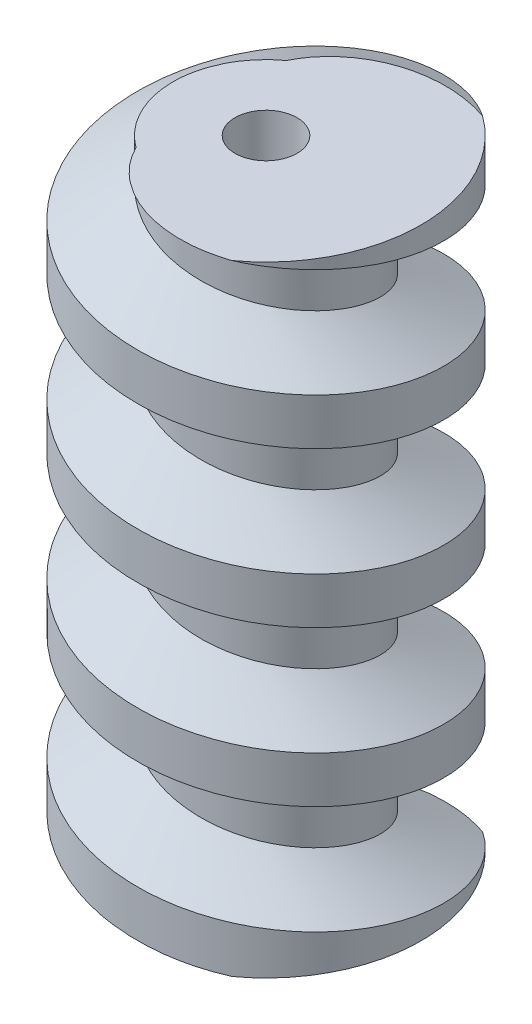
SolidWorks part; units mm, degrees
ref_plane "Front Plane" through (0, 0, 0) normal (0, 0, 1) x (1, 0, 0)
ref_plane "Top Plane" through (0, 0, 0) normal (0, 1, 0) x (1, 0, 0)
ref_plane "Right Plane" through (0, 0, 0) normal (1, 0, 0) x (0, 0, -1)
sketch "Sketch1" plane through (0, 0, 0) normal (0, 1, 0) x (1, 0, 0)
  circle A0 centre (0, 0) radius 10
  dimension "D1" = 20
extrude "Boss-Extrude1" add sketch "Sketch1" along normal blind 40 contours A0
sketch "Sketch2" plane through (0, 0, 0) normal (0, 1, 0) x (1, 0, 0)
  circle A1 centre (0, 0) radius 10
  circle A2 centre (0, 0) radius 10
  dimension "D1" = 0
curve "Helix/Spiral1" pitch 10 height 40 turns 4
ref_plane "Plane1" through (-10, 0, 0) normal (0, 0, 1) x (1, 0, 0)
sketch "Sketch3" plane through (-10, 0, 0) normal (0, 0, 1) x (1, 0, 0)
  line L1 (21.2864, 0) -> (-1.2864, 0) construction
  line L2 (0, 40) -> (0, 0) construction
  line L3 (0, 0) -> (4, 0) construction
  line L4 (4, -1.5) -> (4, 1.5)
  line L5 (4, 1.5) -> (0, 3.5)
  line L6 (4, -1.5) -> (0, -3.5)
  line L7 (0, -3.5) -> (-0.7038, -3.5)
  line L8 (-0.7038, -3.5) -> (-0.7038, 3.5)
  line L9 (-0.7038, 3.5) -> (0, 3.5)
  dimension "D1" = 3
  dimension "D2" = 7
sweep "Cut-Sweep1" cut profiles "Sketch3" path "Helix/Spiral1" align with end faces yes
sketch "Sketch4" plane through (0, 0, 0) normal (0, -1, 0) x (1, 0, 0)
  circle A1 centre (0, 0) radius 2
extrude "Cut-Extrude1" cut sketch "Sketch4" against normal blind 40
